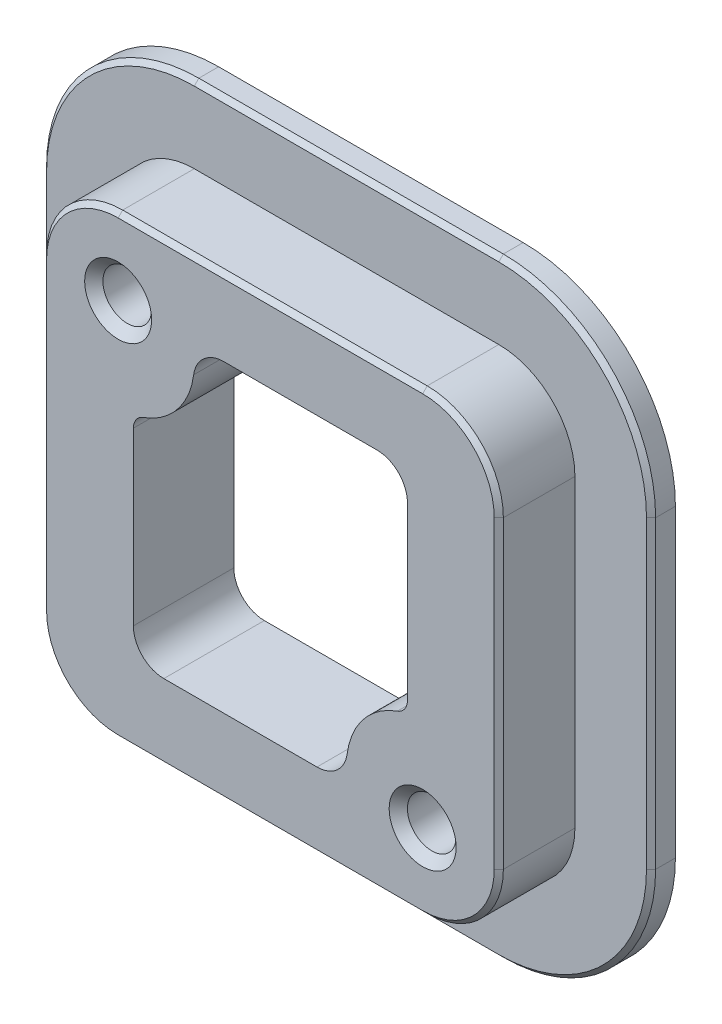
SolidWorks part; units mm, degrees
ref_plane "Ebene vorne" through (0, 0, 0) normal (0, 0, 1) x (1, 0, 0)
ref_plane "Ebene oben" through (0, 0, 0) normal (0, 1, 0) x (1, 0, 0)
ref_plane "Ebene rechts" through (0, 0, 0) normal (1, 0, 0) x (0, 0, -1)
sketch "Skizze1" plane through (0, 0, 0) normal (0, 0, 1) x (1, 0, 0)
  line L1 (15, 15) -> (-15, 15)
  line L2 (15, 15) -> (15, -15)
  line L3 (15, -15) -> (-15, -15)
  line L4 (-15, 15) -> (-15, -15)
  line L5 (15, 15) -> (-15, -15) construction
  line L6 (15, -15) -> (-15, 15) construction
  point P0 (0, 0)
  dimension "D1" = 30
  dimension "D2" = 30
extrude "Grundkörper" add sketch "Skizze1" along normal blind 5
fillet "Verrundung1" radius 5 4 edges at (-15, 15, 2.5) (-15, -15, 2.5) (15, -15, 2.5) (15, 15, 2.5)
sketch "Skizze2" plane through (0, 0, 0) normal (0, 0, -1) x (-1, 0, 0)
  line L8 (20, -10) -> (20, 10)
  line L9 (10, 20) -> (-10, 20)
  line L10 (-20, 10) -> (-20, -10)
  line L11 (-10, -20) -> (10, -20)
  line L12 (20, -10) -> (20, 10)
  line L13 (10, 20) -> (-10, 20)
  line L14 (-20, 10) -> (-20, -10)
  line L15 (-10, -20) -> (10, -20)
  arc A8 (20, 10) -> (10, 20) centre (10, 10) ccw
  arc A9 (-10, 20) -> (-20, 10) centre (-10, 10) ccw
  arc A10 (-20, -10) -> (-10, -20) centre (-10, -10) ccw
  arc A11 (10, -20) -> (20, -10) centre (10, -10) ccw
  arc A12 (20, 10) -> (10, 20) centre (10, 10) ccw
  arc A13 (-10, 20) -> (-20, 10) centre (-10, 10) ccw
  arc A14 (-20, -10) -> (-10, -20) centre (-10, -10) ccw
  arc A15 (10, -20) -> (20, -10) centre (10, -10) ccw
  dimension "D1" = 5
extrude "Absatz" add sketch "Skizze2" along normal blind 1.6
sketch "Skizze3" plane through (0, 0, 5) normal (0, 0, 1) x (1, 0, 0)
  circle A0 centre (-10, 10) radius 1.6
  circle A1 centre (10, -10) radius 1.6
  dimension "D1" = 3.2
  dimension "D2" = 20
extrude "M3 Bohrungen" cut sketch "Skizze3" against normal through all
sketch "Skizze4" plane through (0, 0, -1.6) normal (0, 0, -1) x (-1, 0, 0)
  line L1 (10, 6.5359) -> (13, 8.2679)
  line L2 (13, 8.2679) -> (13, 11.7321)
  line L3 (13, 11.7321) -> (10, 13.4641)
  line L4 (10, 13.4641) -> (7, 11.7321)
  line L5 (7, 11.7321) -> (7, 8.2679)
  line L6 (7, 8.2679) -> (10, 6.5359)
  line L7 (-10, -6.5359) -> (-13, -8.2679)
  line L8 (-13, -8.2679) -> (-13, -11.7321)
  line L9 (-13, -11.7321) -> (-10, -13.4641)
  line L10 (-10, -13.4641) -> (-7, -11.7321)
  line L11 (-7, -11.7321) -> (-7, -8.2679)
  line L12 (-7, -8.2679) -> (-10, -6.5359)
  circle A0 centre (10, 10) radius 3 construction
  circle A1 centre (-10, -10) radius 3 construction
  dimension "D1" = 6
extrude "M3 Schskant" cut sketch "Skizze4" against normal blind 3
sketch "Skizze5" plane through (0, 0, 5) normal (0, 0, 1) x (1, 0, 0)
  line L1 (5, 10) -> (-5, 10)
  line L2 (5, -4) -> (5, -10)
  line L3 (5, -10) -> (-5, -10)
  line L4 (-5, 10) -> (-5, 4)
  line L5 (5, 10) -> (-5, -10) construction
  line L6 (5, -10) -> (-5, 10) construction
  line L7 (-5, -10) -> (-9, -10)
  line L9 (-5, 4) -> (-9, 4)
  line L10 (-9, -10) -> (-9, 4)
  line L11 (5, 10) -> (9, 10)
  line L13 (5, -4) -> (9, -4)
  line L14 (9, 10) -> (9, -4)
  point P0 (0, 0)
  dimension "D1" = 20
  dimension "D2" = 10
  dimension "D3" = 4
  dimension "D4" = 14
extrude "Durchbruch" cut sketch "Skizze5" against normal through all
fillet "Verrundung2" radius 5 2 edges at (5, -4, 1.7) (-5, 4, 1.7)
fillet "Verrundung3" radius 2 4 edges at (5, -10, 1.7) (-9, -10, 1.7) (-5, 10, 1.7) (9, 10, 1.7)
fillet "Verrundung4" radius 1 2 edges at (9, -4, 1.7) (-9, 4, 1.7)
chamfer "Fase1" distance 0.3 angle 45 16 edges at (0, -20, 0) (-17.0711, -17.0711, 0) (17.0711, -17.0711, 0) (-20, 0, 0) (20, 0, 0) (-17.0711, 17.0711, 0) (17.0711, 17.0711, 0) (0, 20, 0) (0, -15, 5) (13.5355, -13.5355, 5) (-13.5355, -13.5355, 5) (15, 0, 5) (-15, 0, 5) (13.5355, 13.5355, 5) (-13.5355, 13.5355, 5) (0, 15, 5)
chamfer "Fase2" distance 0.6 angle 45 2 edges at (-8.4, 10, 5) (11.6, -10, 5)
